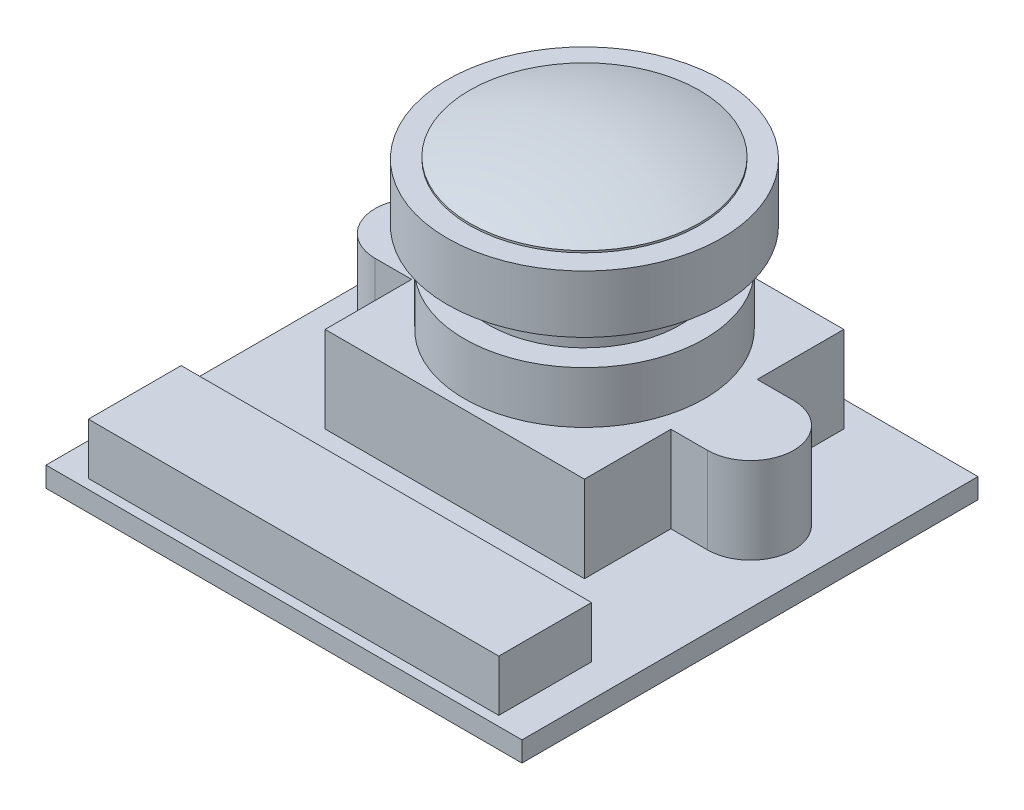
SolidWorks part; units mm, degrees
ref_plane "Front Plane" through (0, 0, 0) normal (0, 0, 1) x (1, 0, 0)
ref_plane "Top Plane" through (0, 0, 0) normal (0, 1, 0) x (1, 0, 0)
ref_plane "Right Plane" through (0, 0, 0) normal (1, 0, 0) x (0, 0, -1)
sketch "Sketch1" plane through (0, 0, 0) normal (0, 1, 0) x (1, 0, 0)
  line L1 (0, 0) -> (24.83, 0)
  line L2 (0, 0) -> (0, 23.79)
  line L3 (0, 23.79) -> (24.83, 23.79)
  line L4 (24.83, 0) -> (24.83, 23.79)
  dimension "D1" = 24.83
  dimension "D2" = 23.79
extrude "Boss-Extrude1" add sketch "Sketch1" along normal blind 1.05
sketch "Sketch2" plane through (0, 1.05, 0) normal (0, 1, 0) x (1, 0, 0)
  line L0 (24.83, 23.79) -> (0, 23.79) construction
  line L1 (3.745, 15.675) -> (7.555, 15.675) construction
  line L2 (3.745, 17.925) -> (5.65, 17.925)
  line L3 (5.65, 22.44) -> (19.18, 22.44)
  line L4 (3.745, 13.425) -> (5.65, 13.425)
  line L5 (5.65, 13.425) -> (5.65, 8.91)
  line L6 (5.65, 22.44) -> (5.65, 17.925)
  line L7 (5.65, 8.91) -> (19.18, 8.91)
  line L8 (19.18, 22.44) -> (19.18, 17.92)
  line L13 (19.18, 13.42) -> (19.18, 8.91)
  line L18 (17.275, 15.67) -> (21.085, 15.67) construction
  line L23 (19.18, 17.92) -> (21.085, 17.92)
  line L24 (19.18, 13.42) -> (21.085, 13.42)
  arc A5 (21.085, 13.42) -> (21.085, 17.92) centre (21.085, 15.67) ccw
  arc A6 (3.745, 17.925) -> (3.745, 13.425) centre (3.745, 15.675) ccw
  point P9 (5.65, 15.675)
  point P10 (20.1325, 17.92)
  point P22 (19.18, 19.45)
  point P27 (23.335, 15.67)
  point P31 (5.65, 11.895)
  dimension "D3" = 4.155
  dimension "D4" = 4.5
  dimension "D1" = 13.53
  dimension "D2" = 13.53
  dimension "D5" = 4.52
  dimension "D6" = 1.35
  dimension "D7" = 4.515
extrude "Boss-Extrude2" add sketch "Sketch2" along normal blind 4.5
sketch "Sketch3" plane through (0, 1.05, 0) normal (0, 1, 0) x (1, 0, 0)
  line L0 (0, 0) -> (24.83, 0) construction
  line L6 (1.71, 0) -> (0, 0)
  line L7 (23.12, 0) -> (24.83, 0) construction
  line L8 (23.12, 0.5) -> (23.12, 0) construction
  line L9 (1.71, 0.5) -> (23.12, 0.5)
  line L10 (1.71, 0.5) -> (1.71, 5.34)
  line L11 (1.71, 5.34) -> (23.12, 5.34)
  line L12 (23.12, 0.5) -> (23.12, 5.34)
  line L13 (1.71, 0.5) -> (1.71, 0) construction
  dimension "D1" = 4.84
  dimension "D2" = 21.41
  dimension "D3" = 0.5
extrude "Boss-Extrude3" add sketch "Sketch3" along normal blind 2.68 contours L9 L12 L11 L10 region at (12.415, 1.05, -2.92)
sketch "Sketch4" plane through (0, 5.55, 0) normal (0, 1, 0) x (1, 0, 0)
  line L0 (12.415, 22.44) -> (12.415, 8.91) construction
  line L1 (19.18, 22.44) -> (5.65, 22.44) construction
  line L2 (5.65, 8.91) -> (19.18, 8.91) construction
  line L3 (1.495, 15.675) -> (23.335, 15.67) construction
  arc A0 (3.745, 17.925) -> (3.745, 13.425) centre (3.745, 15.675) ccw construction
  arc A1 (21.085, 13.42) -> (21.085, 17.92) centre (21.085, 15.67) ccw construction
  circle A2 centre (12.415, 15.675) radius 6.265
  dimension "D1" = 12.53
extrude "Boss-Extrude4" add sketch "Sketch4" along normal blind 2.7
sketch "Sketch5" plane through (0, 8.25, 0) normal (0, 1, 0) x (1, 0, 0)
  line L0 (12.415, 21.94) -> (12.415, 9.41) construction
  line L1 (6.15, 15.675) -> (18.68, 15.675) construction
  circle A0 centre (12.415, 15.675) radius 6.265 construction
  circle A1 centre (12.415, 15.675) radius 5
  dimension "D1" = 10
extrude "Boss-Extrude5" add sketch "Sketch5" along normal blind 2
sketch "Sketch6" plane through (0, 10.25, 0) normal (0, 1, 0) x (1, 0, 0)
  line L0 (12.415, 20.675) -> (12.415, 10.675) construction
  circle A0 centre (12.415, 15.675) radius 5 construction
  circle A1 centre (12.415, 15.675) radius 7.16
  dimension "D1" = 14.32
extrude "Boss-Extrude6" add sketch "Sketch6" along normal blind 3
sketch "Sketch7" plane through (0, 13.25, 0) normal (0, 1, 0) x (1, 0, 0)
  line L0 (12.415, 22.835) -> (12.415, 8.515) construction
  circle A0 centre (12.415, 15.675) radius 7.16 construction
  circle A1 centre (12.415, 15.675) radius 6
  dimension "D1" = 12
extrude "Boss-Extrude7" add sketch "Sketch7" along normal blind 0.1 contours A1
dome "Dome2" faces to dome 1 distance 1 reverse direction no elliptical dome no face at (12.415, 13.35, -9.675) parameters "D1"=1
